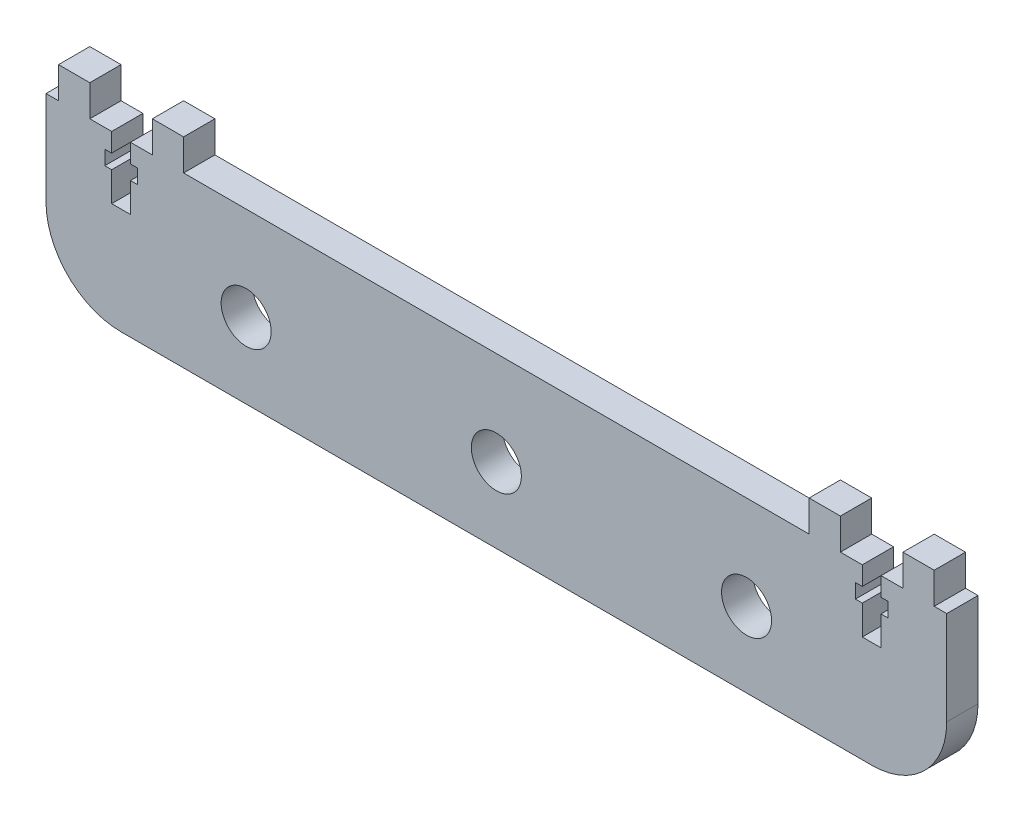
SolidWorks part; units mm, degrees
ref_plane "Front Plane" through (0, 0, 0) normal (0, 0, 1) x (1, 0, 0)
ref_plane "Top Plane" through (0, 0, 0) normal (0, 1, 0) x (1, 0, 0)
ref_plane "Right Plane" through (0, 0, 0) normal (1, 0, 0) x (0, 0, -1)
sketch "Sketch1" plane through (0, 0, 0) normal (0, 0, 1) x (1, 0, 0)
  line L0 (0, 0) -> (0, 77.1281) construction
  line L1 (0, 0) -> (-105.7988, 0) construction
  line L4 (-72, 0) -> (-72, 15)
  line L6 (-72, 15) -> (72, 15)
  line L7 (-60, -12) -> (60, -12)
  line L8 (72, 0) -> (72, 15)
  arc A1 (-72, 0) -> (-60, -12) centre (-60, 0) ccw
  circle A4 centre (-40, 0) radius 4
  circle A5 centre (40, 0) radius 4
  arc A6 (72, 0) -> (60, -12) centre (60, 0) cw
  circle A7 centre (0, 0) radius 4
  point P12 (0, -12)
  point P13 (0, 15)
  point P14 (0, -12)
  point P15 (0, 15)
  line B0 (-57.4, 12) -> (-57.4, 9.7)
  line B1 (-61.5, 9.7) -> (-61.5, 5)
  line B2 (-58.5, 5) -> (-58.5, 9.7)
  line B3 (-57.4, 9.7) -> (-58.5, 9.7)
  line B4 (-60, 15) -> (-60, 3.7792) construction
  line B5 (-58.5, 15) -> (-55, 15)
  line B6 (-55, 20) -> (-50, 20)
  line B7 (-50, 20) -> (-50, 15)
  line B8 (-55, 20) -> (-55, 15)
  line B9 (-61.5, 15) -> (-65, 15)
  line B10 (-65, 15) -> (-65, 20)
  line B11 (-65, 20) -> (-70, 20)
  line B12 (-70, 20) -> (-70, 15)
  line B13 (-58.5, 15) -> (-61.5, 15) construction
  line B14 (-61.5, 15) -> (-61.5, 12)
  line B15 (-61.5, 9.7) -> (-62.6, 9.7)
  line B16 (-62.6, 12) -> (-61.5, 12)
  line B17 (-61.5, 5) -> (-58.5, 5)
  line B18 (-58.5, 12) -> (-57.4, 12)
  line B19 (-62.6, 9.7) -> (-62.6, 12)
  line B20 (-58.5, 12) -> (-58.5, 15)
  line B21 (-60, 5) -> (-60, 15) construction
  line B22 (57.4, 12) -> (57.4, 9.7)
  line B23 (61.5, 9.7) -> (61.5, 5)
  line B24 (58.5, 5) -> (58.5, 9.7)
  line B25 (57.4, 9.7) -> (58.5, 9.7)
  line B26 (60, 15) -> (60, 3.7792) construction
  line B27 (58.5, 15) -> (55, 15)
  line B28 (55, 20) -> (50, 20)
  line B29 (50, 20) -> (50, 15)
  line B30 (55, 20) -> (55, 15)
  line B31 (61.5, 15) -> (65, 15)
  line B32 (65, 15) -> (65, 20)
  line B33 (65, 20) -> (70, 20)
  line B34 (70, 20) -> (70, 15)
  line B35 (58.5, 15) -> (61.5, 15) construction
  line B36 (61.5, 15) -> (61.5, 12)
  line B37 (61.5, 9.7) -> (62.6, 9.7)
  line B38 (62.6, 12) -> (61.5, 12)
  line B39 (61.5, 5) -> (58.5, 5)
  line B40 (58.5, 12) -> (57.4, 12)
  line B41 (62.6, 9.7) -> (62.6, 12)
  line B42 (58.5, 12) -> (58.5, 15)
  line B43 (60, 5) -> (60, 15) construction
  dimension "D3" = 12
  dimension "D4" = 12
  dimension "D6" = 8
  dimension "D1" = 60
  dimension "D7" = 8
  dimension "D2" = 40
  dimension "D5" = 15
sketch_block_instance "Insert M3 plots ep 5mm-1"
sketch_block "Insert M3 plots ep 5mm" parameters "D1"=10, "D2"=5, "D3"=5
sketch_block_instance "Decoupe Insert M3-4"
sketch_block "Decoupe Insert M3" parameters "D1"=5.2, "D2"=3, "D3"=2.3, "D4"=3, "D5"=10
sketch_block_instance "Insert M3 plots ep 5mm-4"
extrude "Boss-Extrude2" add sketch "Sketch1" along normal blind 5 contours B40 B42 L6 B20 B18 B0 B3 B2 B17 B1 B15 B19 B16 B14 L4 A1 L7 A6 L8 B36 B38 B41 B37 B23 B39 B24 B25 B22 A4 A5 | B30 B28 B29 L6 | B34 B33 B32 L6 | B11 B12 L6 B10 | B6 B8 L6 B7 region at (-70.5349, 7.5, 0) region at (-67.5, 17.5, 0) region at (67.5, 17.5, 0) region at (-52.5, 17.5, 0) region at (52.5, 17.5, 0)
